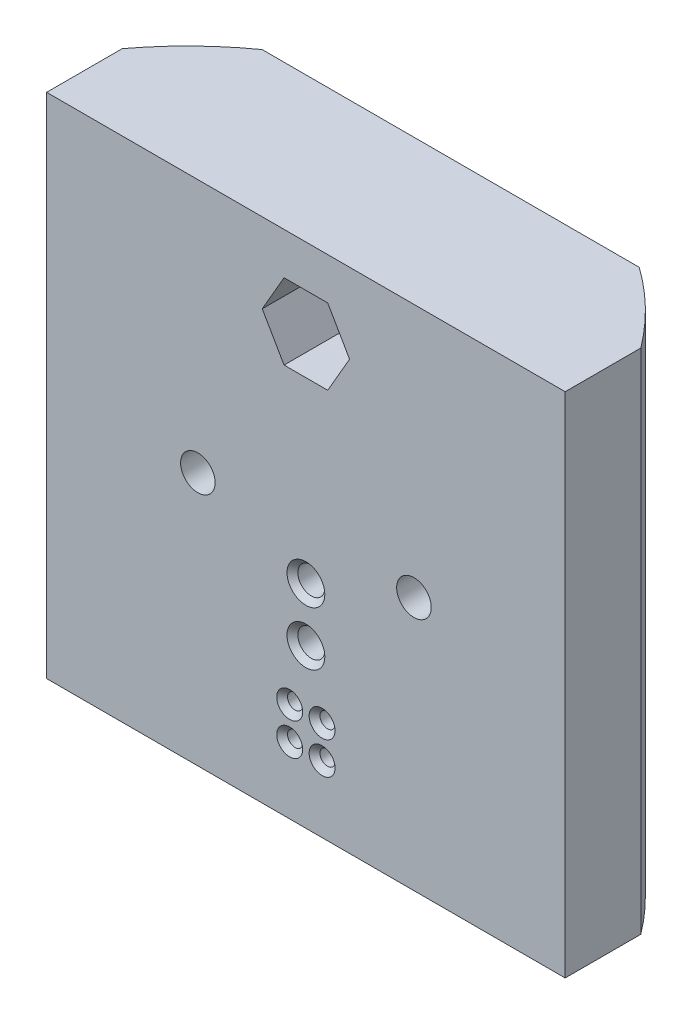
SolidWorks part; units mm, degrees
ref_plane "Front Plane" through (0, 0, 0) normal (0, 0, 1) x (1, 0, 0)
ref_plane "Top Plane" through (0, 0, 0) normal (0, 1, 0) x (1, 0, 0)
ref_plane "Right Plane" through (0, 0, 0) normal (1, 0, 0) x (0, 0, -1)
sketch "Sketch1" plane through (0, 0, 0) normal (0, 0, 1) x (1, 0, 0)
  line L0 (-2.275, -128.15) -> (-2.275, -128.6)
  line L1 (2.275, -128.15) -> (2.275, -128.6)
  line L2 (-2.275, -133.15) -> (-2.275, -134.025)
  line L3 (2.275, -133.15) -> (2.275, -134.025)
  line L11 (-2.275, -128.15) -> (2.275, -128.15)
  line L12 (2.275, -128.15) -> (2.275, -123.6)
  line L13 (2.275, -123.6) -> (-2.275, -123.6)
  line L14 (-2.275, -123.6) -> (-2.275, -128.15)
  line L15 (-2.275, -128.15) -> (2.275, -128.15)
  line L16 (2.275, -128.15) -> (2.275, -123.6)
  line L17 (2.275, -123.6) -> (-2.275, -123.6)
  line L18 (-2.275, -123.6) -> (-2.275, -128.15)
  line L24 (-2.275, -133.15) -> (2.275, -133.15)
  line L25 (2.275, -133.15) -> (2.275, -128.6)
  line L26 (2.275, -128.6) -> (-2.275, -128.6)
  line L27 (-2.275, -128.6) -> (-2.275, -133.15)
  line L28 (-2.275, -133.15) -> (2.275, -133.15)
  line L29 (2.275, -133.15) -> (2.275, -128.6)
  line L30 (2.275, -128.6) -> (-2.275, -128.6)
  line L31 (-2.275, -128.6) -> (-2.275, -133.15)
  line L37 (0, -123.6) -> (0, -142.4) construction
  line L39 (7, -120.5) -> (-7, -120.5)
  line L40 (7, -120.5) -> (7, -145.5)
  line L41 (7, -145.5) -> (-7, -145.5)
  line L42 (-7, -120.5) -> (-7, -145.5)
  line L43 (7, -120.5) -> (-7, -145.5) construction
  line L44 (7, -145.5) -> (-7, -120.5) construction
  line L45 (-1, -142.4) -> (1, -142.4)
  line L46 (1, -142.4) -> (1, -141.625)
  line L47 (1, -141.625) -> (3.8, -141.625)
  line L48 (3.8, -141.625) -> (3.8, -134.025)
  line L49 (3.8, -134.025) -> (-3.8, -134.025)
  line L50 (-3.8, -134.025) -> (-3.8, -141.625)
  line L51 (-3.8, -141.625) -> (-1, -141.625)
  line L52 (-1, -141.625) -> (-1, -142.4)
  line L53 (-1, -142.4) -> (1, -142.4)
  line L54 (1, -142.4) -> (1, -141.625)
  line L55 (1, -141.625) -> (3.8, -141.625)
  line L56 (3.8, -141.625) -> (3.8, -134.025)
  line L57 (3.8, -134.025) -> (-3.8, -134.025)
  line L58 (-3.8, -134.025) -> (-3.8, -141.625)
  line L59 (-3.8, -141.625) -> (-1, -141.625)
  line L60 (-1, -141.625) -> (-1, -142.4)
  circle A0 centre (0, -125.875) radius 1.275
  circle A1 centre (0, -130.875) radius 1.275
  circle A2 centre (-1.5, -139.325) radius 0.65
  circle A3 centre (-1.5, -136.325) radius 0.65
  circle A4 centre (1.5, -136.325) radius 0.65
  circle A5 centre (1.5, -139.325) radius 0.65
  point P25 (0, -133)
  dimension "D4" = 2.55
  dimension "D5" = 1.3
  dimension "D6" = 25
  dimension "D7" = 14
  dimension "D1" = 0.2
  dimension "D2" = 0.2
  dimension "D3" = 0.2
extrude "Boss-Extrude1" add sketch "Sketch1" against normal blind 6.4 contours L39 L42 L41 L40 L60 L59 L58 L57 L31 L18 L17 L16 L29 L56 L55 L54 L53 region at (6.7135, -133, 0)
sketch "Sketch3" plane through (0, 0, 0) normal (0, 0, 1) x (1, 0, 0)
  line L4 (7, -120.5) -> (-7, -120.5)
  line L5 (-7, -120.5) -> (-7, -145.5)
  line L6 (-7, -145.5) -> (7, -145.5)
  line L7 (7, -145.5) -> (7, -120.5)
  line L8 (7, -120.5) -> (-7, -120.5)
  line L9 (-7, -120.5) -> (-7, -145.5)
  line L10 (-7, -145.5) -> (7, -145.5)
  line L11 (7, -145.5) -> (7, -120.5)
  circle A0 centre (-1.5, -139.325) radius 0.7
  circle A1 centre (-1.5, -136.325) radius 0.7
  circle A2 centre (1.5, -136.325) radius 0.7
  circle A3 centre (1.5, -139.325) radius 0.7
  circle A4 centre (0, -130.875) radius 1.25
  circle A5 centre (0, -125.875) radius 1.25
  dimension "D2" = 2.5
  dimension "D3" = 1.4
  dimension "D1" = 0
extrude "Boss-Extrude3" add sketch "Sketch3" along normal blind 7
chamfer "Chamfer1" distance 0.5 angle 45 6 edges at (2.2, -139.325, 7) (-0.8, -139.325, 7) (-0.8, -136.325, 7) (2.2, -136.325, 7) (1.25, -130.875, 7) (1.25, -125.875, 7)
sketch "Sketch4" plane through (0, -145.5, 0) normal (0, -1, 0) x (1, 0, 0)
  line L0 (-7, -6.4) -> (-17.4539, -6.4)
  line L1 (-7, 7) -> (-27.9106, 7)
  line L2 (7, -6.4) -> (17.4539, -6.4)
  line L3 (7, 7) -> (27.9106, 7)
  line L4 (-24, 0) -> (-24, 7)
  line L5 (24, 0) -> (24, 7)
  circle A4 centre (0, 18) radius 30
  arc A5 (-24, 0) -> (24, 0) centre (0, 18) ccw construction
  line M2 (7, -6.4) -> (7, 7)
  line M4 (-7, 7) -> (-7, -6.4)
extrude "Boss-Extrude4" add sketch "Sketch4" against normal up to surface (25 mm away) contours L1 A4 L0 M4 | L2 A4 L3 M2 region at (-14.9215, -145.5, 0.7207) region at (14.9215, -145.5, 0.7207) up to face at (0, -120.5, 0.3)
sketch "Sketch5" plane through (0, -120.5, 0) normal (0, 1, 0) x (1, 0, 0)
  line L2 (17.4539, 6.4) -> (-17.4539, 6.4)
  line L3 (-24, -7) -> (24, -7)
  line L4 (17.4539, 6.4) -> (-17.4539, 6.4)
  line L5 (-24, -7) -> (24, -7)
  line L8 (-24, 0) -> (-24, -7)
  line L9 (-24, 0) -> (-24, -7)
  line L10 (24, -7) -> (24, 0)
  line L11 (24, -7) -> (24, 0)
  arc A2 (-17.4539, 6.4) -> (-24, 0) centre (0, -18) ccw
  arc A3 (24, 0) -> (17.4539, 6.4) centre (0, -18) ccw
  arc A4 (-17.4539, 6.4) -> (-24, 0) centre (0, -18) ccw
  arc A5 (24, 0) -> (17.4539, 6.4) centre (0, -18) ccw
  dimension "D1" = 0
extrude "Boss-Extrude5" add sketch "Sketch5" along normal blind 22
sketch "Sketch6" plane through (0, 0, 7) normal (0, 0, 1) x (1, 0, 0)
  line L0 (0, -98.5) -> (0, -145.5) construction
  line L1 (-24, -98.5) -> (24, -98.5) construction
  line L2 (-24, -145.5) -> (24, -145.5) construction
  circle A0 centre (0, -105.875) radius 2.25
  circle A3 centre (0, -105.875) radius 2.25 construction
  dimension "D2" = 4.5
extrude "Cut-Extrude1" cut sketch "Sketch6" against normal up to next
sketch "Sketch7" plane through (0, 0, 7) normal (0, 0, 1) x (1, 0, 0)
  line L1 (4.0415, -105.875) -> (2.0207, -102.375)
  line L2 (2.0207, -102.375) -> (-2.0207, -102.375)
  line L3 (-2.0207, -102.375) -> (-4.0415, -105.875)
  line L4 (-4.0415, -105.875) -> (-2.0207, -109.375)
  line L5 (-2.0207, -109.375) -> (2.0207, -109.375)
  line L6 (2.0207, -109.375) -> (4.0415, -105.875)
  circle A0 centre (0, -105.875) radius 3.5 construction
  dimension "D1" = 7
extrude "Cut-Extrude2" cut sketch "Sketch7" against normal offset from surface (7.4 mm away) 6 up to face at (2.25, -105.875, -6.4)
sketch "Sketch9" plane through (0, 0, -6.4) normal (0, 0, -1) x (-1, 0, 0)
  line L0 (-24, -122) -> (24, -122) construction
  line L1 (-24, -98.5) -> (-24, -145.5) construction
  line L2 (24, -98.5) -> (24, -145.5) construction
  line L3 (0, -98.5) -> (0, -145.5) construction
  line L4 (-17.4539, -98.5) -> (17.4539, -98.5) construction
  line L5 (-17.4539, -145.5) -> (17.4539, -145.5) construction
  circle A0 centre (-10, -122) radius 1.6
  circle A1 centre (10, -122) radius 1.6
  dimension "D1" = 3.2
  dimension "D2" = 20
extrude "Cut-Extrude4" cut sketch "Sketch9" against normal up to next
sketch "Sketch10" plane through (0, 0, -6.4) normal (0, 0, -1) x (-1, 0, 0)
  line L0 (0, -98.5) -> (0, -145.5) construction
  line L1 (-10, -125.2332) -> (-7.2, -123.6166)
  line L2 (-7.2, -123.6166) -> (-7.2, -120.3834)
  line L3 (-7.2, -120.3834) -> (-10, -118.7668)
  line L4 (-10, -118.7668) -> (-12.8, -120.3834)
  line L5 (-12.8, -120.3834) -> (-12.8, -123.6166)
  line L6 (-12.8, -123.6166) -> (-10, -125.2332)
  line L7 (-17.4539, -98.5) -> (17.4539, -98.5) construction
  line L8 (-17.4539, -145.5) -> (17.4539, -145.5) construction
  line L9 (12.8, -123.6166) -> (10, -125.2332)
  line L10 (12.8, -120.3834) -> (12.8, -123.6166)
  line L11 (10, -118.7668) -> (12.8, -120.3834)
  line L12 (7.2, -120.3834) -> (10, -118.7668)
  line L13 (7.2, -123.6166) -> (7.2, -120.3834)
  line L14 (10, -125.2332) -> (7.2, -123.6166)
  circle A0 centre (-10, -122) radius 2.8 construction
  dimension "D1" = 5.6
extrude "Cut-Extrude5" cut sketch "Sketch10" against normal offset from surface (7.4 mm away) 6 up to face at (11.6, -122, 7)
